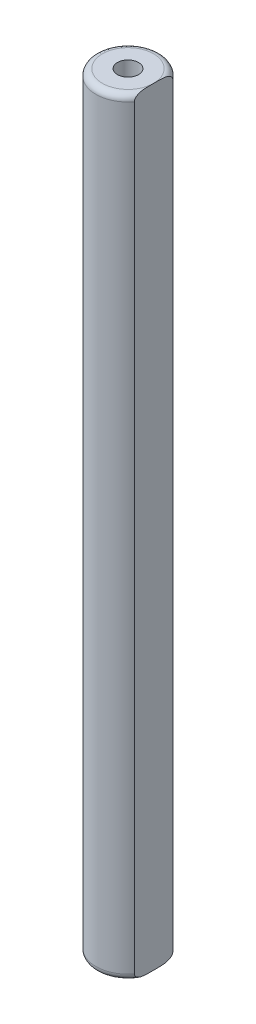
SolidWorks part; units mm, degrees
material "Alumina"
ref_plane "Front Plane" through (0, 0, 0) normal (0, 0, 1) x (1, 0, 0)
ref_plane "Top Plane" through (0, 0, 0) normal (0, 1, 0) x (1, 0, 0)
ref_plane "Right Plane" through (0, 0, 0) normal (1, 0, 0) x (0, 0, -1)
sketch "Sketch1" plane through (0, 0, 0) normal (0, 1, 0) x (1, 0, 0)
  circle A0 centre (0, 0) radius 2.5
  dimension "D1" = 5
extrude "Boss-Extrude1" add sketch "Sketch1" along normal blind 30
sketch "Sketch2" plane through (0, 30, 0) normal (0, 1, 0) x (1, 0, 0)
  circle A0 centre (0, 0) radius 0.825
  dimension "D1" = 1.65
extrude "Cut-Extrude1" cut sketch "Sketch2" against normal blind 5
sketch "Sketch3" plane through (0, 30, 0) normal (0, 1, 0) x (1, 0, 0)
  line L0 (2, 1.5) -> (2, -1.5)
  circle A0 centre (0, 0) radius 2.5 construction
  arc A1 (2, -1.5) -> (2, 1.5) centre (0, 0) ccw
  dimension "D1" = 3
extrude "Cut-Extrude2" cut sketch "Sketch3" against normal through all
fillet "Fillet1" radius 0.5 1 edges at (-2.5, 30, 0)
mirror "Mirror1" about plane through (0, 0, 0) normal (0, 1, 0) of "Fillet1", "Cut-Extrude2", "Cut-Extrude1", "Boss-Extrude1"
